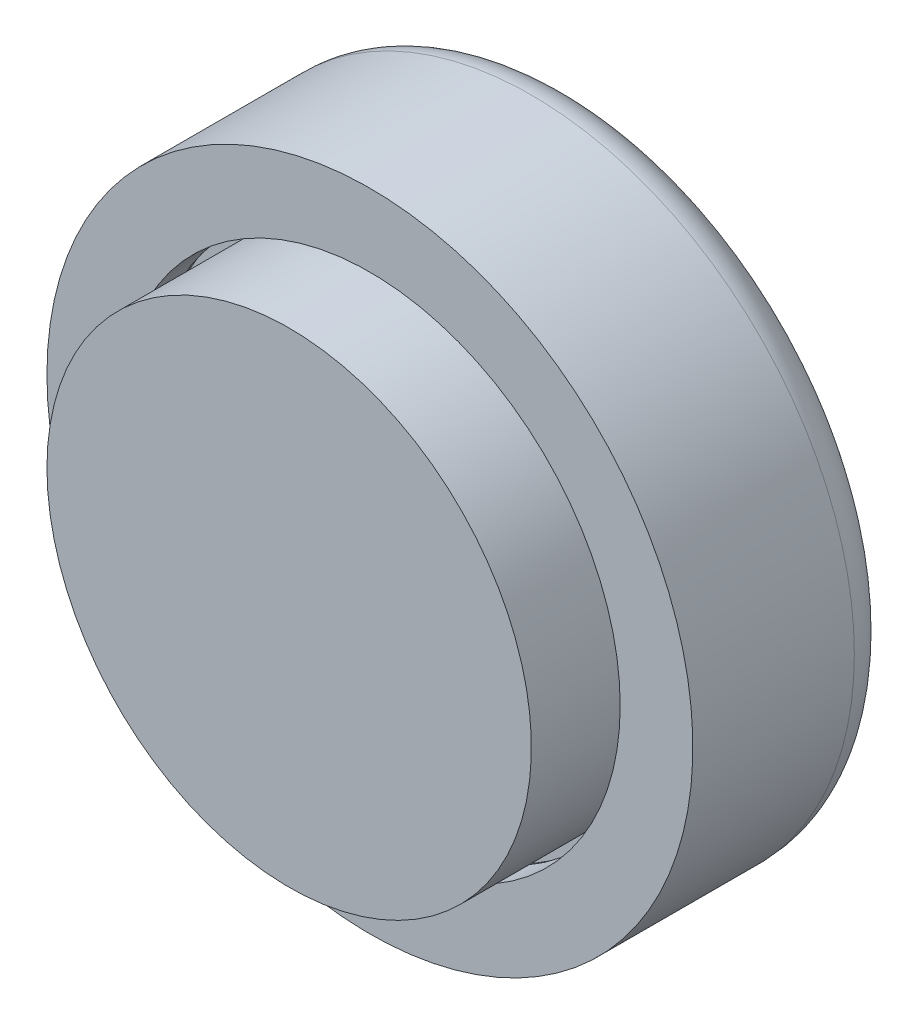
SolidWorks part; units mm, degrees
other "btm"
other "cap"
ref_plane "Front Plane" through (0, 0, 0) normal (0, 0, 1) x (1, 0, 0)
ref_plane "Top Plane" through (0, 0, 0) normal (0, 1, 0) x (1, 0, 0)
ref_plane "Right Plane" through (0, 0, 0) normal (1, 0, 0) x (0, 0, -1)
sketch "Sketch3" plane through (0, 0, 0) normal (0, 1, 0) x (1, 0, 0)
  line L0 (0, 0) -> (6, 0)
  line L1 (6, 0) -> (6, 3)
  line L2 (6, 3) -> (6.25, 3)
  line L3 (6.25, 3) -> (6.25, 4)
  line L4 (6.25, 4) -> (4, 4)
  line L5 (4, 4) -> (4, 1)
  line L6 (4, 1) -> (0, 1)
  line L7 (0, 1) -> (0, 0)
  line L8 (0, 0) -> (0, -5.9108) construction
  line L9 (0, 6) -> (2, 6)
  line L10 (6.45, 6) -> (6.45, 2.8)
  line L11 (6.45, 2.8) -> (6.2, 2.8)
  line L12 (6.2, 2.8) -> (6.2, 2)
  line L13 (6.2, 2) -> (8, 2)
  line L14 (8, 2) -> (8, 7)
  line L15 (8, 7) -> (0, 7)
  line L16 (0, 7) -> (0, 6)
  line L17 (3.5, 6) -> (3.5, 4)
  line L18 (3.5, 4) -> (2, 4)
  line L19 (2, 4) -> (2, 6)
  line L20 (3.5, 6) -> (6.45, 6)
  dimension "D1" = 6
  dimension "D2" = 0.25
  dimension "D3" = 4
  dimension "D4" = 1
  dimension "D5" = 1
  dimension "D6" = 4
  dimension "D7" = 8
  dimension "D8" = 2
  dimension "D9" = 0.2
  dimension "D10" = 0.2
  dimension "D11" = 0.2
  dimension "D12" = 2
  dimension "D13" = 7
  dimension "D14" = 0.5
  dimension "D15" = 1.5
  dimension "D16" = 2
revolve "Revolve3" add sketch "Sketch3" angle 360 about L8 region at (4.0434, 0, -1.5408)
revolve "Revolve4" add sketch "Sketch3<3>" angle 360 about L8 region at (0.0943, 0, -6.5)
sketch "Sketch3<3>" plane through (0, 0, 0) normal (0, 1, 0) x (1, 0, 0) same geometry as "Sketch3"
sketch "Sketch4" plane through (0, 0, -7) normal (0, 0, -1) x (-1, 0, 0)
  line L0 (-5, -1.75) -> (5, -1.75) construction
  line L1 (0, -1.75) -> (0, 0) construction
  text T0 "<b>DRS</b>"
  dimension "D1" = 1.75
  dimension "D2" = 10
extrude "Cut-Extrude2" cut sketch "Sketch4" against normal blind 0.4
fillet "Fillet1" radius 1 1 edges at (-8, 0, -7)
sketch "Sketch5" plane through (0, 0, -6) normal (0, 0, 1) x (1, 0, 0)
  line L0 (0, -3.85) -> (0, 3.85) construction
  line L1 (-1, 3) -> (1, 3)
  line L2 (-1, 3) -> (-1, 4.5)
  line L3 (-1, 4.5) -> (1, 4.5)
  line L4 (1, 3) -> (1, 4.5)
  line L5 (0, 0) -> (0, 6.8491) construction
  circle A1 centre (0, 0) radius 3.5 construction
  circle A2 centre (0, 0) radius 3.5 construction
  point P6 (0, 4.5)
  dimension "D2" = 0.5
  dimension "D3" = 1
  dimension "D1" = 2
extrude "Boss-Extrude1" add sketch "Sketch5" along normal up to surface (2 mm away) up to face at (-2, 0, -4)
sketch "Sketch6" plane through (0, 0, -4) normal (0, 0, -1) x (-1, 0, 0)
  line L0 (-1.2, 2.8) -> (1.2, 2.8)
  line L1 (1.2, 2.8) -> (1.2, 4.7)
  line L2 (1.2, 4.7) -> (-1.2, 4.7)
  line L3 (-1.2, 4.7) -> (-1.2, 2.8)
  line L4 (-1, 3) -> (1, 3)
  line L5 (-1, 4.5) -> (-1, 3)
  line L6 (1, 4.5) -> (-1, 4.5)
  line L7 (1, 3) -> (1, 4.5)
  line L8 (-1, 3) -> (1, 3) construction
  line L9 (-1, 4.5) -> (-1, 3) construction
  line L10 (1, 4.5) -> (-1, 4.5) construction
  line L11 (1, 3) -> (1, 4.5) construction
  dimension "D1" = 0
  dimension "D2" = 0.2
extrude "Cut-Extrude3" cut sketch "Sketch6" against normal up to surface (3 mm away) up to face at (-4, 0, -1)
